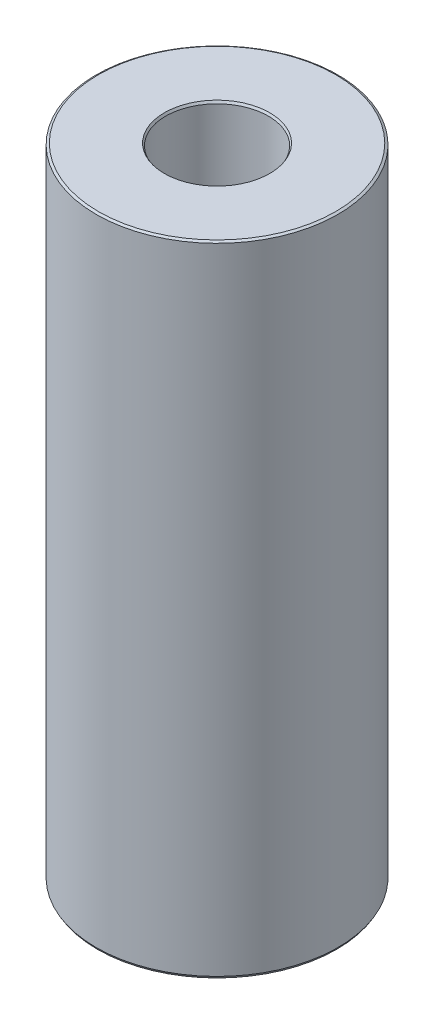
SolidWorks part; units mm, degrees
ref_plane "Front Plane" through (0, 0, 0) normal (0, 0, 1) x (1, 0, 0)
ref_plane "Top Plane" through (0, 0, 0) normal (0, 1, 0) x (1, 0, 0)
ref_plane "Right Plane" through (0, 0, 0) normal (1, 0, 0) x (0, 0, -1)
sketch "Sketch1" plane through (0, 0, 0) normal (0, 1, 0) x (1, 0, 0)
  circle A0 centre (0, 0) radius 55
  dimension "SLEEVE_OD" = 110
extrude "Boss-Extrude1" add sketch "Sketch1" along normal blind 290.5061
sketch "Sketch2" plane through (0, 0, 0) normal (0, 1, 0) x (1, 0, 0)
  circle A0 centre (0, 0) radius 23.3755
  dimension "BORE_D" = 46.7509
extrude "Cut-Extrude1" cut sketch "Sketch2" along normal through all
chamfer "Chamfer1" distance 0.5965 angle 60 4 edges at (0, 290.5061, 23.3755) (0, 0, 23.3755) (0, 0, 55) (0, 290.5061, 55) first distance on face at (0, 290.5061, 23.3755) first distance on face at (0, 0, 23.3755) first distance on face at (0, 290.5061, 55)
